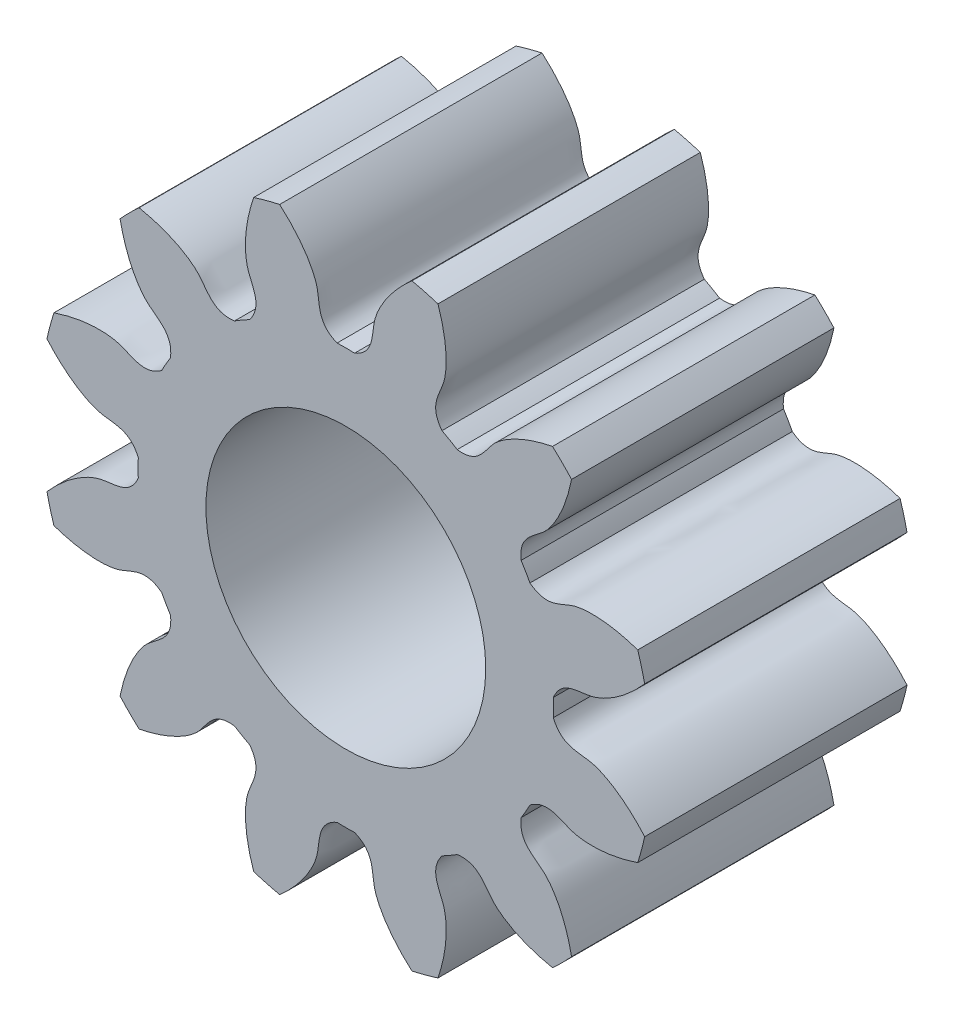
SolidWorks part; units mm, degrees
ref_plane "前视基准面" through (0, 0, 0) normal (0, 0, 1) x (1, 0, 0)
ref_plane "上视基准面" through (0, 0, 0) normal (0, 1, 0) x (1, 0, 0)
ref_plane "右视基准面" through (0, 0, 0) normal (1, 0, 0) x (0, 0, -1)
other "Configuration Table"
sketch "草图1" plane through (0, 0, 0) normal (0, 0, 1) x (1, 0, 0)
  circle A0 centre (0, 0) radius 3.5
extrude "凸台-拉伸1" add sketch "草图1" along normal blind 3
ref_axis "基准轴1" through (0, 0, 3) along (0, 0, -1)
sketch "草图2" plane through (0, 0, 0) normal (0, 0, 1) x (1, 0, 0)
  line L0 (0, 0) -> (0, 3.5) construction
  circle A0 centre (0, 0) radius 3.5 construction
  arc A1 (0.1004, 2.3729) -> (-0.1004, 2.3729) centre (0, 0) ccw
  arc A2 (1.7488, 3.9475) -> (-1.7488, 3.9475) centre (0, 0) ccw
  spline S0 degree 3 poles (0.1004, 2.3729) (0.3404, 2.4747) (0.2872, 2.6724) (0.3381, 2.8447) (0.3413, 2.855) (0.3451, 2.8662) (0.3495, 2.8784) (0.3546, 2.8915) (0.3603, 2.9056) (0.3668, 2.9206) (0.374, 2.9366) (0.3821, 2.9533) (0.3909, 2.971) (0.4007, 2.9894) (0.4114, 3.0086) (0.423, 3.0286) (0.4356, 3.0493) (0.4492, 3.0707) (0.4639, 3.0928) (0.4796, 3.1155) (0.4965, 3.1388) (0.5145, 3.1626) (0.5337, 3.187) (0.554, 3.2119) (0.5756, 3.2372) (0.5985, 3.2629) (0.6226, 3.289) (0.648, 3.3154) (0.6748, 3.342) (0.7028, 3.369) (0.7323, 3.3961) (0.7631, 3.4234) (0.7954, 3.4507) (0.829, 3.4782) (0.8641, 3.5057) (0.9006, 3.5331) (0.9385, 3.5604) (0.978, 3.5877) (1.0189, 3.6147) (1.0613, 3.6416) (1.1052, 3.6681) (1.1506, 3.6944) (1.1975, 3.7203) (1.2459, 3.7457) (1.2958, 3.7707) (1.3472, 3.7952) (1.4001, 3.8191) (1.4546, 3.8424) (1.5105, 3.865) (1.5679, 3.8869) (1.6472, 3.9154) (1.7078, 3.9351) (1.7488, 3.9475) knots 0 0 0 0 0.218015 0.222044 0.226546 0.231522 0.236972 0.242897 0.249295 0.256167 0.263513 0.271332 0.279626 0.288394 0.297636 0.307351 0.317541 0.328204 0.339341 0.350953 0.363038 0.375597 0.38863 0.402137 0.416118 0.430573 0.445502 0.460904 0.476781 0.493132 0.509956 0.527255 0.545027 0.563273 0.581994 0.601188 0.620856 0.640998 0.661614 0.682704 0.704268 0.726305 0.748817 0.771803 0.795262 0.819196 0.843603 0.868484 0.89384 0.919669 0.945972 1 1 1 1
  spline S1 degree 3 poles (-0.1004, 2.3729) (-0.3404, 2.4747) (-0.2872, 2.6724) (-0.3381, 2.8447) (-0.3413, 2.855) (-0.3451, 2.8662) (-0.3495, 2.8784) (-0.3546, 2.8915) (-0.3603, 2.9056) (-0.3668, 2.9206) (-0.374, 2.9366) (-0.3821, 2.9533) (-0.3909, 2.971) (-0.4007, 2.9894) (-0.4114, 3.0086) (-0.423, 3.0286) (-0.4356, 3.0493) (-0.4492, 3.0707) (-0.4639, 3.0928) (-0.4796, 3.1155) (-0.4965, 3.1388) (-0.5145, 3.1626) (-0.5337, 3.187) (-0.554, 3.2119) (-0.5756, 3.2372) (-0.5985, 3.2629) (-0.6226, 3.289) (-0.648, 3.3154) (-0.6748, 3.342) (-0.7028, 3.369) (-0.7323, 3.3961) (-0.7631, 3.4234) (-0.7954, 3.4507) (-0.829, 3.4782) (-0.8641, 3.5057) (-0.9006, 3.5331) (-0.9385, 3.5604) (-0.978, 3.5877) (-1.0189, 3.6147) (-1.0613, 3.6416) (-1.1052, 3.6681) (-1.1506, 3.6944) (-1.1975, 3.7203) (-1.2459, 3.7457) (-1.2958, 3.7707) (-1.3472, 3.7952) (-1.4001, 3.8191) (-1.4546, 3.8424) (-1.5105, 3.865) (-1.5679, 3.8869) (-1.6472, 3.9154) (-1.7078, 3.9351) (-1.7488, 3.9475) knots 0 0 0 0 0.218015 0.222044 0.226546 0.231522 0.236972 0.242897 0.249295 0.256167 0.263513 0.271332 0.279626 0.288394 0.297636 0.307351 0.317541 0.328204 0.339341 0.350953 0.363038 0.375597 0.38863 0.402137 0.416118 0.430573 0.445502 0.460904 0.476781 0.493132 0.509956 0.527255 0.545027 0.563273 0.581994 0.601188 0.620856 0.640998 0.661614 0.682704 0.704268 0.726305 0.748817 0.771803 0.795262 0.819196 0.843603 0.868484 0.89384 0.919669 0.945972 1 1 1 1
extrude "切除-拉伸1" cut sketch "草图2" along normal through all
pattern_circular "阵列(圆周)1" count 12 every 30 about axis through (0, 0, 3) along (0, 0, -1) of "切除-拉伸1"
sketch "草图3" plane through (0, 0, 0) normal (0, 0, 1) x (1, 0, 0)
  circle A0 centre (0, 0) radius 3 construction
  dimension "Dn" = 6
sketch "草图4" plane through (0, 0, 3) normal (0, 0, 1) x (1, 0, 0)
  circle A0 centre (0, 0) radius 1.6
  dimension "D1" = 3.2
extrude "切除-拉伸2" cut sketch "草图4" against normal up to next
